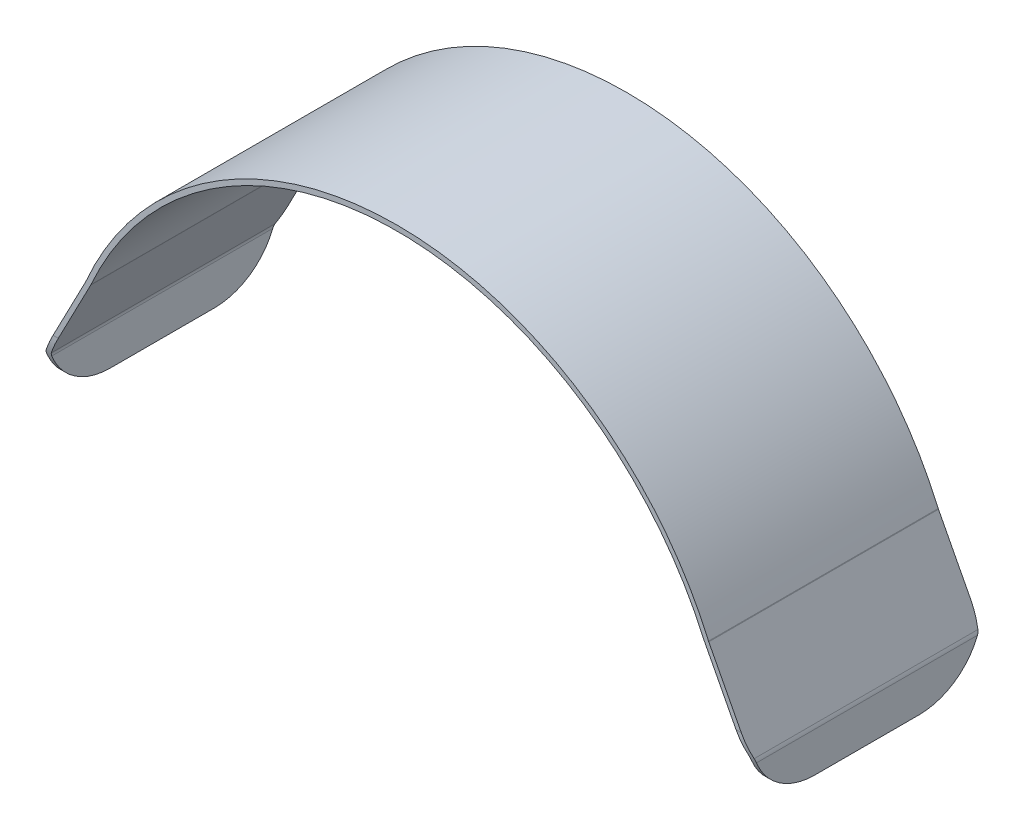
SolidWorks part; units mm, degrees
material "Acrylic (Medium-high impact)"
ref_plane "Front Plane" through (0, 0, 0) normal (0, 0, 1) x (1, 0, 0)
ref_plane "Top Plane" through (0, 0, 0) normal (0, 1, 0) x (1, 0, 0)
ref_plane "Right Plane" through (0, 0, 0) normal (1, 0, 0) x (0, 0, -1)
sketch "Sketch2" plane through (0, 0, 0) normal (0, 0, 1) x (1, 0, 0)
  line L0 (-212.725, 0) -> (-215.9, 0)
  line L1 (212.725, 0) -> (215.9, 0)
  line L2 (-215.9, 0) -> (-215.9, 25.4)
  line L3 (-212.725, 0) -> (-212.725, 25.4)
  line L4 (212.725, 0) -> (212.725, 25.4)
  line L5 (215.9, 0) -> (215.9, 25.4)
  line L6 (-215.9, 25.4) -> (-189.4552, 76.2)
  line L7 (-212.725, 25.4) -> (-186.2802, 76.2)
  line L8 (-212.725, 25.4) -> (-166.2015, 25.4) construction
  line L9 (212.725, 25.4) -> (186.2802, 76.2)
  line L10 (215.9, 25.4) -> (189.4552, 76.2)
  line L11 (212.725, 25.4) -> (148.3275, 25.4) construction
  arc A4 (-189.4552, 76.2) -> (189.4552, 76.2) centre (0, -5.5159) cw
  arc A5 (-186.2802, 76.2) -> (186.2802, 76.2) centre (0, -5.957) cw
  dimension "D3" = 25.4
  dimension "D6" = 25.4
  dimension "D7" = 3.175
  dimension "D8" = 62.5
  dimension "D12" = 3.175
  dimension "D13" = 209.55
  dimension "D1" = 212.725
  dimension "D2" = 212.725
  dimension "D4" = 3.175
  dimension "D5" = 3.175
  dimension "D9" = 50.8
  dimension "D10" = 50.8
  dimension "D11" = 62.5
extrude "Boss-Extrude1" add sketch "Sketch2" along normal mid plane 139.7
fillet "Fillet1" radius 38.1 1 edges at (214.3125, 0, -69.85)
fillet "Fillet2" radius 38.1 1 edges at (214.3125, 0, 69.85)
fillet "Fillet3" radius 38.1 1 edges at (-214.3125, 0, 69.85)
fillet "Fillet4" radius 38.1 1 edges at (-214.3125, 0, -69.85)
fillet "Fillet5" radius 5.08 4 edges at (215.9, 25.4, 0) (-215.9, 25.4, 0) (-212.725, 25.4, 0) (212.725, 25.4, 0)
fillet "Fillet6" radius 5.08 4 edges at (-189.4552, 76.2, 0) (-186.2802, 76.2, 0) (186.2802, 76.2, 0) (189.4552, 76.2, 0)
